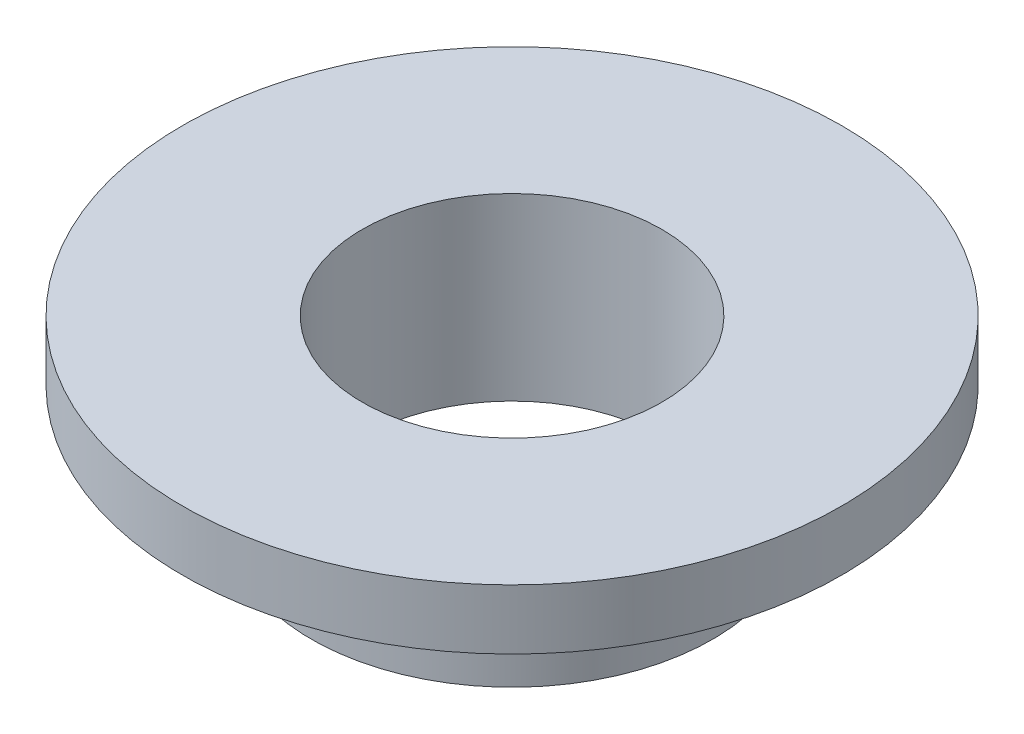
SolidWorks part; units mm, degrees
material "Сталь ШХ15 ГОСТ 801-78"
ref_plane "Plane1" through (0, 0, 0) normal (0, 0, 1) x (1, 0, 0)
ref_plane "Plane2" through (0, 0, 0) normal (0, 1, 0) x (1, 0, 0)
ref_plane "Plane3" through (0, 0, 0) normal (1, 0, 0) x (0, 0, -1)
sketch "Эскиз1" plane through (0, 0, 0) normal (0, 0, 1) x (1, 0, 0)
  line L6 (0, 0) -> (0, 6.4893) construction
  line L7 (5, 0) -> (5, 6)
  line L8 (5, 6) -> (11, 6)
  line L9 (11, 6) -> (11, 4)
  line L10 (11, 4) -> (6.7, 4)
  line L11 (6.7, 4) -> (6.7, 0)
  line L12 (6.7, 0) -> (5, 0)
  dimension "D1" = 5
  dimension "D2" = 6.7
  dimension "D3" = 11
  dimension "D4" = 2
  dimension "D5" = 6
  dimension "D6" = 0
revolve "Повернуть1" add sketch "Эскиз1" angle 360 about L6
